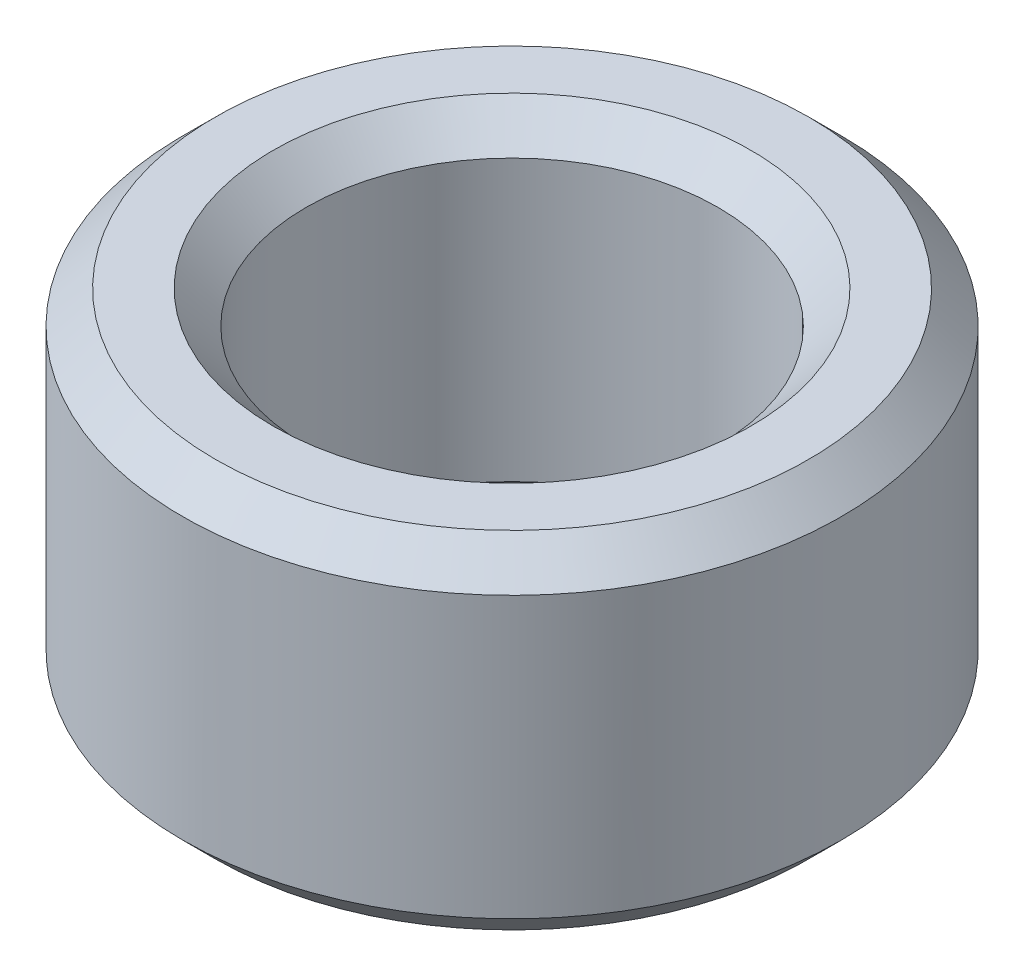
SolidWorks part; units mm, degrees
ref_plane "Front Plane" through (0, 0, 0) normal (0, 0, 1) x (1, 0, 0)
ref_plane "Top Plane" through (0, 0, 0) normal (0, 1, 0) x (1, 0, 0)
ref_plane "Right Plane" through (0, 0, 0) normal (1, 0, 0) x (0, 0, -1)
sketch "Sketch1" plane through (0, 0, 0) normal (0, 1, 0) x (1, 0, 0)
  circle A0 centre (0, 0) radius 1.25
  circle A1 centre (0, 0) radius 2
extrude "Boss-Extrude1" add sketch "Sketch1" along normal blind 2.1
chamfer "Chamfer1" distance 0.2 angle 45 4 edges at (0, 0, 1.25) (0, 2.1, 1.25) (0, 0, 2) (0, 2.1, 2)
